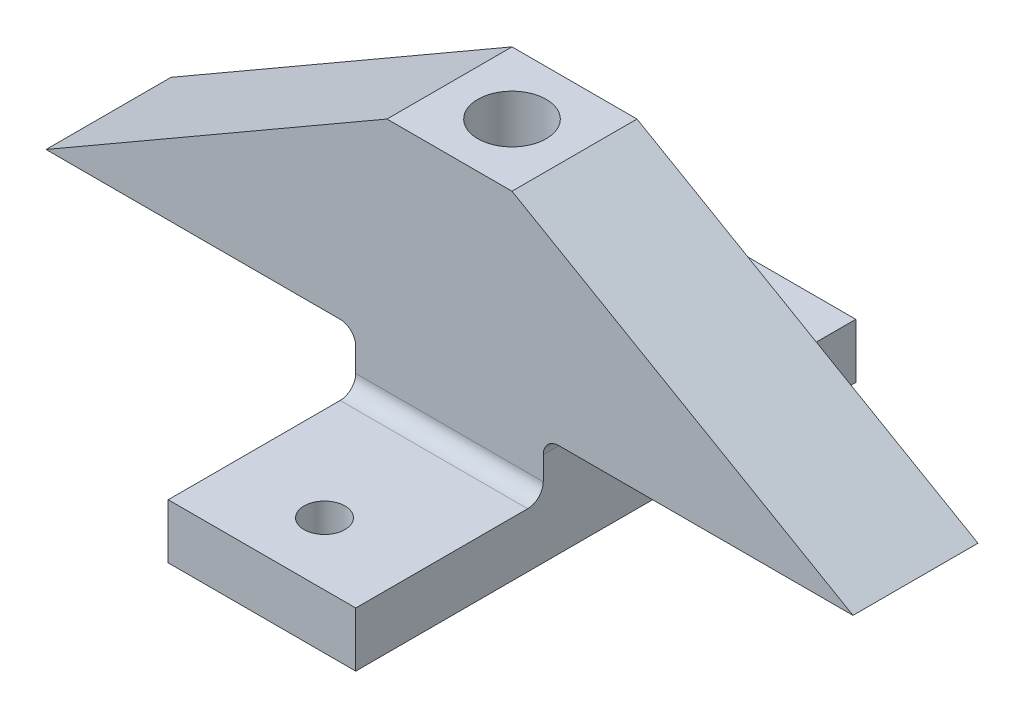
SolidWorks part; units mm, degrees
material "PET"
ref_plane "Front Plane" through (0, 0, 0) normal (0, 0, 1) x (1, 0, 0)
ref_plane "Top Plane" through (0, 0, 0) normal (0, 1, 0) x (1, 0, 0)
ref_plane "Right Plane" through (0, 0, 0) normal (1, 0, 0) x (0, 0, -1)
sketch "Sketch1" plane through (0, 0, 0) normal (0, 0, 1) x (1, 0, 0)
  line L0 (0, 0) -> (0, 22.225)
  line L1 (0, 22.225) -> (-62.932, 22.225)
  line L2 (-62.932, 22.225) -> (6.35, 62.225)
  line L3 (6.35, 62.225) -> (31.75, 62.225)
  line L4 (31.75, 62.225) -> (101.032, 22.225)
  line L5 (101.032, 22.225) -> (38.1, 22.225)
  line L6 (38.1, 22.225) -> (38.1, 0)
  line L7 (38.1, 0) -> (0, 0)
  point P9 (19.05, 62.225)
  point P10 (19.05, 0)
  dimension "D1" = 40
  dimension "D2" = 38.1
  dimension "D3" = 30
  dimension "D4" = 30
  dimension "D5" = 25.4
  dimension "D6" = 22.225
extrude "Boss-Extrude1" add sketch "Sketch1" along normal blind 25.4
sketch "Sketch2" plane through (0, 0, 25.4) normal (0, 0, 1) x (1, 0, 0)
  line L0 (38.1, 0) -> (38.1, 22.225) construction
  line L1 (0, 0) -> (38.1, 0)
  line L2 (0, 0) -> (0, 11.1125)
  line L3 (0, 11.1125) -> (38.1, 11.1125)
  line L4 (38.1, 0) -> (38.1, 11.1125)
extrude "Boss-Extrude2" add sketch "Sketch2" along normal blind 38.1
sketch "Sketch3" plane through (0, 0, 0) normal (0, 0, -1) x (-1, 0, 0)
  line L0 (0, 22.225) -> (0, 0) construction
  line L1 (-38.1, 0) -> (0, 0)
  line L2 (-38.1, 0) -> (-38.1, 11.1125)
  line L3 (-38.1, 11.1125) -> (0, 11.1125)
  line L4 (0, 0) -> (0, 11.1125)
extrude "Boss-Extrude3" add sketch "Sketch3" along normal blind 38.1
hole_wizard "Ø0.328in Dowel Hole1" positions "Sketch4" profile "Sketch5" hole size "Ø1.0" standard "ISO" end condition through all
sketch "Sketch4" plane through (0, 11.1125, 0) normal (0, 1, 0) x (1, 0, 0)
  point P0 (19.05, 25.4)
  point P2 (19.05, -50.8)
  dimension "D1" = 12.7
  dimension "D2" = 19.05
  dimension "D3" = 12.7
  dimension "D4" = 19.05
sketch "Sketch5" plane through (19.05, 11.1125, -25.4) normal (1, 0, 0) x (0, 0, 1)
  line L0 (0, 0) -> (0, 11.1125)
  line L1 (0, 11.1125) -> (4.1656, 11.1125)
  line L2 (4.1656, 11.1125) -> (4.1656, 0)
  line L5 (4.1656, 0) -> (0, 0)
  line L11 (0, -6.35) -> (0, 107.95) construction
  dimension "Thru Hole Dia." = 8.3312
  dimension "Thru Hole Depth" = 11.1125
hole_wizard "Ø0.55in Dowel Hole2" positions "Sketch7" profile "Sketch6" hole size "Ø1.0" standard "ISO"
sketch "Sketch7" plane through (0, 62.225, 0) normal (0, 1, 0) x (1, 0, 0)
  point P0 (19.05, -12.7)
  dimension "D1" = 12.7
  dimension "D2" = 12.7
sketch "Sketch6" plane through (19.05, 62.225, 12.7) normal (1, 0, 0) x (0, 0, 1)
  line L0 (0, 0) -> (0, 39.2261)
  line L1 (0, 39.2261) -> (6.9469, 35.052)
  line L2 (6.9469, 35.052) -> (6.9469, 0)
  line L5 (6.9469, 0) -> (0, 0)
  line L10 (0, 39.2261) -> (-6.9469, 35.052) construction
  line L11 (0, -6.35) -> (0, 107.95) construction
  dimension "Hole Dia." = 13.8938
  dimension "Hole Depth" = 35.052
  dimension "Drill Angle" = 118
fillet "Fillet1" radius 3.175 4 edges at (38.1, 22.225, 12.7) (19.05, 11.1125, 0) (0, 22.225, 12.7) (19.05, 11.1125, 25.4)
